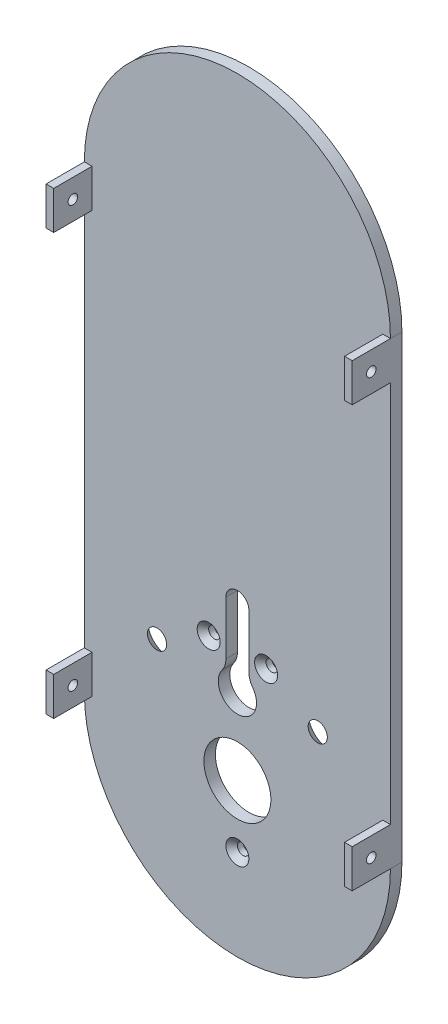
SolidWorks part; units mm, degrees
ref_plane "Front Plane" through (0, 0, 0) normal (0, 0, 1) x (1, 0, 0)
ref_plane "Top Plane" through (0, 0, 0) normal (0, 1, 0) x (1, 0, 0)
ref_plane "Right Plane" through (0, 0, 0) normal (1, 0, 0) x (0, 0, -1)
sketch "Sketch3" plane through (0, 0, 0) normal (0, 0, 1) x (1, 0, 0)
  line L1 (-40, 0) -> (40, 0)
  line L2 (-40, 0) -> (-40, 150)
  line L3 (-30, 160) -> (30, 160)
  line L4 (40, 0) -> (40, 150)
  circle A0 centre (0, 0) radius 40
  arc A1 (30, 160) -> (40, 150) centre (30, 150) cw
  arc A2 (-40, 150) -> (-30, 160) centre (-30, 150) cw
  circle A3 centre (0, 120) radius 40
  point P11 (-40, 160)
  dimension "D2" = 80
  dimension "D4" = 10
  dimension "D5" = 40
  dimension "D6" = 120
  dimension "D1" = 160
  dimension "D3" = 80
extrude "Boss-Extrude4" add sketch "Sketch3" along normal blind 3 contours L1 A0 | L1 A0 | A3 L2 A0 L4 | A3 region at (0, 16.9765, 0) region at (0, 60, 0) region at (0, -16.9765, 0) region at (0, 120, 0)
sketch "Sketch6" plane through (0, 0, 0) normal (0, 0, -1) x (-1, 0, 0)
  circle A0 centre (-7.5, 29.0071) radius 1.5
  circle A1 centre (7.5, 29.0071) radius 1.5
  circle A3 centre (0, -16.25) radius 1.5
  circle A4 centre (0, 7) radius 25 construction
  circle A6 centre (0, 0) radius 8.75
  point P11 (0, 0)
  dimension "D3" = 23.25
  dimension "D4" = 15
  dimension "D5" = 7.5
  dimension "D6" = 3
  dimension "D7" = 3
  dimension "D8" = 3
  dimension "D9" = 17.5
  dimension "D10" = 7
  dimension "D11" = 0
  dimension "D1" = 23.25
  dimension "D2" = 23.25
extrude "Cut-Extrude2" cut sketch "Sketch6" against normal through all
chamfer "Chamfer1" distance 1.5 angle 45 3 edges at (-1.5, -16.25, 3) (-9, 29.0071, 3) (6, 29.0071, 3)
sketch "Sketch9" plane through (0, 0, 0) normal (0, 0, -1) x (-1, 0, 0)
  line L0 (3, 40) -> (3, 20)
  line L1 (-3, 40) -> (-3, 20.8535)
  circle A0 centre (0, 20) radius 3
  circle A1 centre (0, 40) radius 3
  circle A2 centre (0, 20) radius 5
  dimension "D1" = 6
  dimension "D2" = 20
  dimension "D3" = 6
  dimension "D5" = 10
  dimension "D4" = 20
sketch "Sketch12" plane through (0, 0, 3) normal (0, 0, 1) x (1, 0, 0)
  line L0 (40, 0) -> (40, 120) construction
  line L1 (40, 120) -> (38, 120)
  line L2 (40, 120) -> (40, 110)
  line L3 (40, 110) -> (38, 110)
  line L4 (38, 120) -> (38, 110)
  line L5 (-40, 0) -> (-40, 120) construction
  line L6 (-40, 120) -> (-38, 120)
  line L7 (-40, 120) -> (-40, 110)
  line L8 (-40, 110) -> (-38, 110)
  line L9 (-38, 120) -> (-38, 110)
  line L11 (-40, 10) -> (-38, 10)
  line L12 (-40, 10) -> (-40, 0)
  line L13 (-40, 0) -> (-38, 0)
  line L14 (-38, 10) -> (-38, 0)
  line L15 (40, 0) -> (38, 0)
  line L16 (40, 0) -> (40, 10)
  line L17 (40, 10) -> (38, 10)
  line L18 (38, 0) -> (38, 10)
  arc A0 (-40, 0) -> (40, 0) centre (0, 0) ccw construction
  point P25 (0, 0)
  point P29 (-0.0363, 0.0997)
  point P30 (0, 0)
  point P31 (0, 0)
  dimension "D1" = 10
  dimension "D2" = 10
  dimension "D3" = 110
  dimension "D4" = 110
  dimension "D5" = 2
  dimension "D6" = 2
  dimension "D7" = 2
  dimension "D9" = 10
  dimension "D10" = 2
  dimension "D12" = 10
extrude "Boss-Extrude7" add sketch "Sketch12" along normal blind 10
sketch "Sketch13" plane through (-40, 0, 0) normal (-1, 0, 0) x (0, 0, 1)
  line L1 (13, 120) -> (3, 120) construction
  line L2 (13, 10) -> (13, 0) construction
  line L3 (13, 10) -> (3, 10) construction
  line L4 (3, 120) -> (3, 160) construction
  circle A0 centre (8, 115) radius 1.25
  circle A1 centre (8, 5) radius 1.25
  dimension "D1" = 5
  dimension "D2" = 5
  dimension "D3" = 2.5
  dimension "D4" = 2.5
  dimension "D5" = 5
  dimension "D6" = 5
extrude "Cut-Extrude8" cut sketch "Sketch13" against normal through all
sketch "Sketch14" plane through (0, 0, 0) normal (0, 0, -1) x (-1, 0, 0)
  circle A0 centre (-21, 21.5) radius 2.5
  circle A1 centre (21, 21.5) radius 2.5
  dimension "D1" = 5
  dimension "D2" = 5
  dimension "D3" = 42
  dimension "D4" = 21
  dimension "D5" = 21.5
extrude "Cut-Extrude9" cut sketch "Sketch14" against normal through all
chamfer "Chamfer2" distance 3 angle 45 2 edges at (-23.5, 21.5, 0) (18.5, 21.5, 0)
extrude "Cut-Extrude10" cut sketch "Sketch9" against normal through all contours A2 L0 A1 L1 | A1 | A2 A0 | A0 region at (0, 40, 0) region at (0, 31.1765, 0) region at (0, 20, 0) region at (-4.3456, 22.1728, 0)
fillet "Fillet1" radius 5 2 edges at (3, 24, 1.5) (-3, 24, 1.5)
